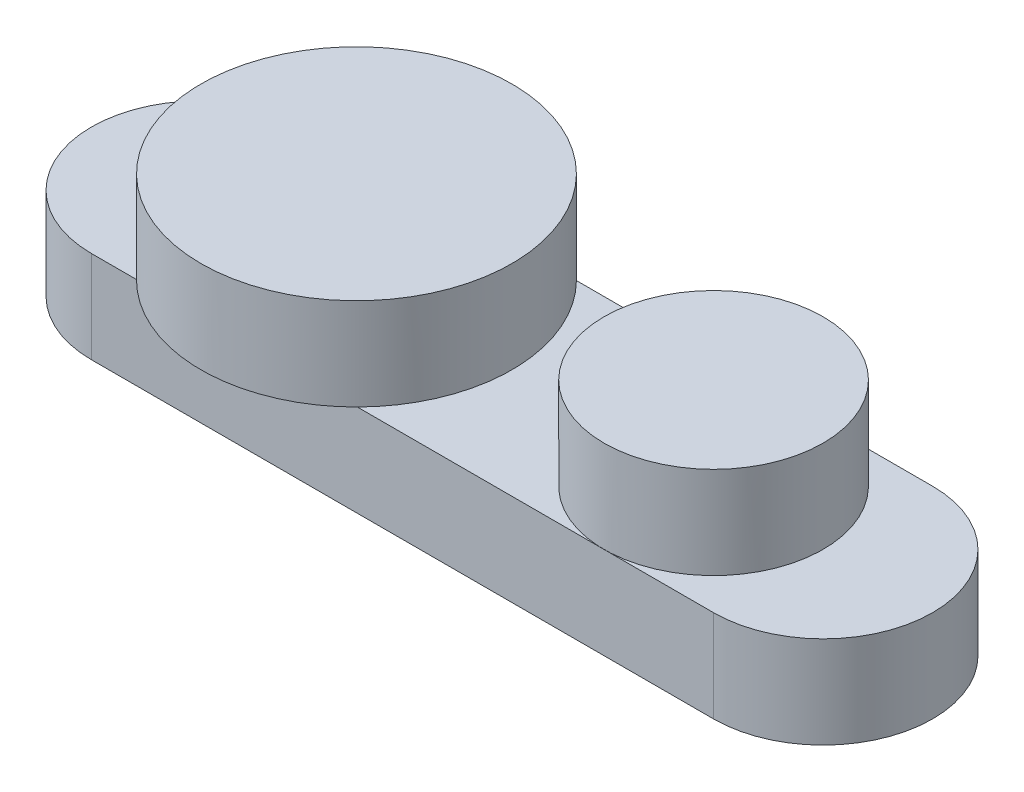
SolidWorks part; units mm, degrees
ref_plane "Спереди" through (0, 0, 0) normal (0, 0, 1) x (1, 0, 0)
ref_plane "Сверху" through (0, 0, 0) normal (0, 1, 0) x (1, 0, 0)
ref_plane "Справа" through (0, 0, 0) normal (1, 0, 0) x (0, 0, -1)
sketch "Эскиз1" plane through (0, 0, 0) normal (0, 1, 0) x (1, 0, 0)
  line L0 (0, 0) -> (5, 0) construction
  line L1 (21.9, 0) -> (26.9, 0) construction
  line L2 (38.8, 0) -> (43.8, 0) construction
  line L3 (13.45, 8.45) -> (13.45, 13.45) construction
  line L4 (13.45, -8.45) -> (13.45, -13.45) construction
  circle A0 centre (13.45, 0) radius 8.45
  circle A1 centre (32.85, 0) radius 5.95
  dimension "D1" = 16.9
  dimension "D2" = 11.9
  dimension "D3" = 5
extrude "Бобышка-Вытянуть1" add sketch "Эскиз1" along normal blind 5
sketch "Эскиз2" plane through (0, 0, 0) normal (0, -1, 0) x (1, 0, 0)
  line L0 (5, 0) -> (38.8, 0) construction
  line L1 (5, 0) -> (38.8, 0) construction
  line L2 (5, 5.95) -> (38.8, 5.95)
  line L3 (5, -5.95) -> (38.8, -5.95)
  circle A0 centre (13.45, 0) radius 8.45 construction
  circle A1 centre (32.85, 0) radius 5.95 construction
  arc A2 (5, 5.95) -> (5, -5.95) centre (5, 0) ccw
  arc A3 (38.8, -5.95) -> (38.8, 5.95) centre (38.8, 0) ccw
  point P8 (21.9, 0)
extrude "Бобышка-Вытянуть2" add sketch "Эскиз2" along normal blind 5
